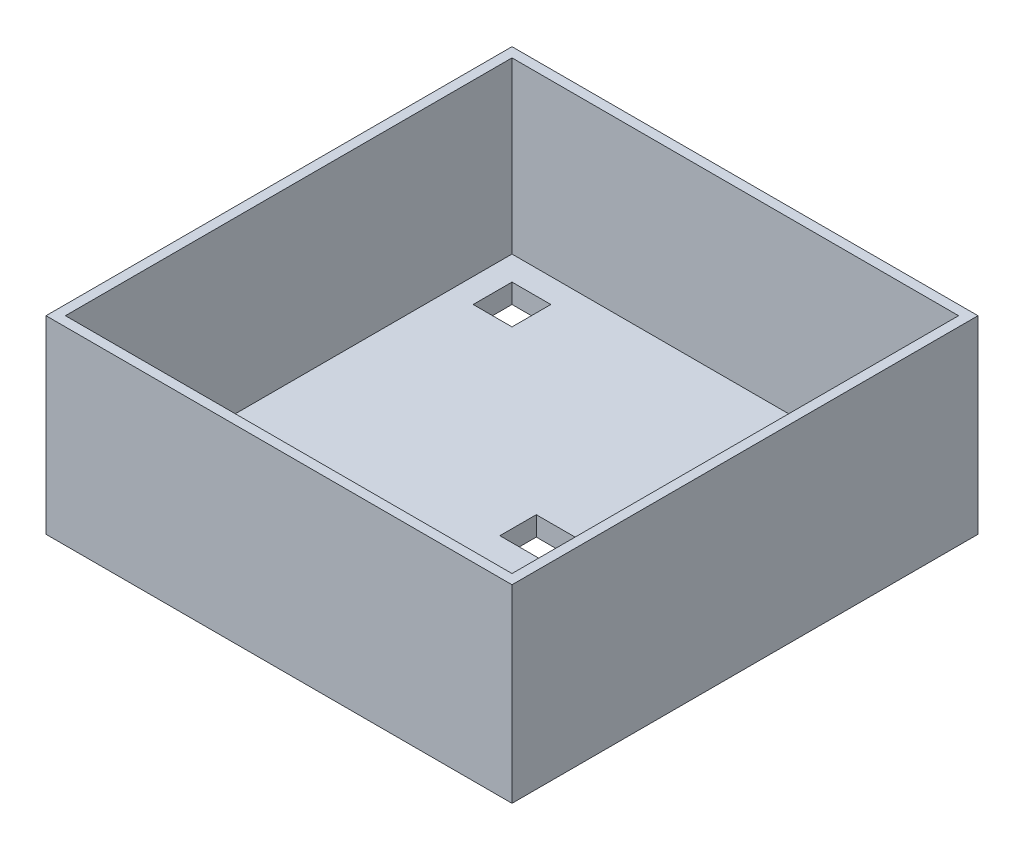
SolidWorks part; units mm, degrees
ref_plane "Front Plane" through (0, 0, 0) normal (0, 0, 1) x (1, 0, 0)
ref_plane "Top Plane" through (0, 0, 0) normal (0, 1, 0) x (1, 0, 0)
ref_plane "Right Plane" through (0, 0, 0) normal (1, 0, 0) x (0, 0, -1)
sketch "Sketch1" plane through (0, 0, 0) normal (0, 1, 0) x (1, 0, 0)
  line L1 (-50, -50) -> (50, -50)
  line L2 (-50, -50) -> (-50, 50)
  line L3 (-50, 50) -> (50, 50)
  line L4 (50, -50) -> (50, 50)
  line L5 (-50, -50) -> (50, 50) construction
  line L6 (-50, 50) -> (50, -50) construction
  point P0 (0, 0)
  dimension "D1" = 100
extrude "Boss-Extrude1" add sketch "Sketch1" along normal blind 4
sketch "Sketch2" plane through (0, 4, 0) normal (0, 1, 0) x (1, 0, 0)
  line L0 (46, -46) -> (46, 46)
  line L1 (46, 46) -> (-46, 46)
  line L2 (-46, 46) -> (-46, -46)
  line L3 (-46, -46) -> (46, -46)
  line L4 (50, -50) -> (50, 50)
  line L5 (50, 50) -> (-50, 50)
  line L6 (-50, 50) -> (-50, -50)
  line L7 (-50, -50) -> (50, -50)
  line L8 (50, -50) -> (50, 50)
  line L9 (50, 50) -> (-50, 50)
  line L10 (-50, 50) -> (-50, -50)
  line L11 (-50, -50) -> (50, -50)
  dimension "D1" = 0
  dimension "D2" = 4
extrude "Boss-Extrude2" add sketch "Sketch2" along normal blind 35
sketch "Sketch3" plane through (0, 0, -50) normal (0, 0, -1) x (-1, 0, 0)
  line L0 (-50, 39) -> (50, 39) construction
  line L1 (2, 35) -> (-2, 35)
  line L2 (2, 35) -> (2, 39)
  line L3 (2, 39) -> (-2, 39)
  line L4 (-2, 35) -> (-2, 39)
  line L5 (2, 35) -> (-2, 39) construction
  line L6 (2, 39) -> (-2, 35) construction
  point P0 (0, 37)
  dimension "D1" = 4
extrude "Cut-Extrude1" cut sketch "Sketch3" against normal up to surface (4 mm away) up to face at (0, 21.5, -46)
sketch "Sketch4" plane through (0, 4, 0) normal (0, 1, 0) x (1, 0, 0)
  line L1 (9.75, -0.5) -> (-1.75, -0.5)
  line L2 (9.75, -0.5) -> (9.75, -17)
  line L3 (9.75, -17) -> (-1.75, -17)
  line L4 (-1.75, -0.5) -> (-1.75, -17)
  line L5 (9.75, -0.5) -> (-1.75, -17) construction
  line L6 (9.75, -17) -> (-1.75, -0.5) construction
  line L7 (14, 19) -> (-6, 19)
  line L8 (14, 19) -> (14, -21)
  line L9 (14, -21) -> (-6, -21)
  line L10 (-6, 19) -> (-6, -21)
  line L11 (14, 19) -> (-6, -21) construction
  line L12 (14, -21) -> (-6, 19) construction
  line L17 (-46, -46) -> (46, -46) construction
  line L26 (46, -46) -> (46, 46) construction
  line L28 (12.25, -19.5) -> (7.25, -19.5)
  line L29 (12.25, -19.5) -> (12.25, -14.5)
  line L30 (12.25, -14.5) -> (7.25, -14.5)
  line L31 (7.25, -19.5) -> (7.25, -14.5)
  line L32 (12.25, -19.5) -> (7.25, -14.5) construction
  line L33 (12.25, -14.5) -> (7.25, -19.5) construction
  line L34 (-4.25, -19.5) -> (0.75, -19.5)
  line L35 (-4.25, -19.5) -> (-4.25, -14.5)
  line L36 (-4.25, -14.5) -> (0.75, -14.5)
  line L37 (0.75, -19.5) -> (0.75, -14.5)
  line L38 (-4.25, -19.5) -> (0.75, -14.5) construction
  line L39 (-4.25, -14.5) -> (0.75, -19.5) construction
  line L40 (12.25, 2) -> (7.25, 2)
  line L41 (12.25, 2) -> (12.25, -3)
  line L42 (12.25, -3) -> (7.25, -3)
  line L43 (7.25, 2) -> (7.25, -3)
  line L44 (12.25, 2) -> (7.25, -3) construction
  line L45 (12.25, -3) -> (7.25, 2) construction
  line L46 (-4.25, 2) -> (0.75, 2)
  line L47 (-4.25, 2) -> (-4.25, -3)
  line L48 (-4.25, -3) -> (0.75, -3)
  line L49 (0.75, 2) -> (0.75, -3)
  line L50 (-4.25, 2) -> (0.75, -3) construction
  line L51 (-4.25, -3) -> (0.75, 2) construction
  point P0 (4, -8.75)
  point P5 (4, -1)
  dimension "D1" = 11.5
  dimension "D2" = 16.5
  dimension "D3" = 32
  dimension "D4" = 25
  dimension "D5" = 40
  dimension "D6" = 20
  dimension "D7" = 4
  dimension "D8" = 2.5
  dimension "D9" = 2.5
extrude "Boss-Extrude3" add sketch "Sketch4" along normal blind 2.5 contours L49 L46 L47 L48 L4 L1 | L40 L43 L1 L2 L42 L41 | L31 L28 L29 L30 L2 L3 | L34 L37 L3 L4 L36 L35 region at (10.1667, 4, 0.0833) region at (-2.1667, 4, 0.0833) region at (10.1667, 4, 17.4167) region at (-2.1667, 4, 17.4167)
sketch "Sketch5" plane through (0, 4, 0) normal (0, 1, 0) x (1, 0, 0)
  line L1 (4, -13) -> (-1.75, -13)
  line L2 (4, -13) -> (4, -17)
  line L3 (4, -17) -> (-1.75, -17)
  line L4 (-1.75, -13) -> (-1.75, -17)
  line L5 (4, -13) -> (-1.75, -17) construction
  line L6 (4, -17) -> (-1.75, -13) construction
  point P0 (1.125, -15)
  dimension "D1" = 4
  dimension "D2" = 5.75
extrude "Cut-Extrude2" cut sketch "Sketch5" against normal up to surface (4 mm away) up to face at (0, 0, 0)
sketch "Sketch7" plane through (0, 4, 0) normal (0, 1, 0) x (1, 0, 0)
  line L0 (4, -13) -> (-1.75, -13) construction
  line L1 (-4.25, -19.5) -> (5, -19.5)
  line L2 (-4.25, -19.5) -> (-4.25, -12)
  line L3 (-4.25, -12) -> (5, -12)
  line L4 (5, -19.5) -> (5, -12)
  line L5 (4, -17) -> (4, -13) construction
  line L6 (-46, 46) -> (-46, -46) construction
  line L7 (12.25, 2) -> (3, 2)
  line L8 (12.25, 2) -> (12.25, -5.5)
  line L9 (12.25, -5.5) -> (3, -5.5)
  line L10 (3, 2) -> (3, -5.5)
  line L11 (-41, 33) -> (-33, 33)
  line L12 (-41, 33) -> (-41, 41)
  line L13 (-41, 41) -> (-33, 41)
  line L14 (-33, 33) -> (-33, 41)
  line L15 (-41, 33) -> (-33, 41) construction
  line L16 (-41, 41) -> (-33, 33) construction
  line L17 (2, 46) -> (-2, 46) construction
  point P9 (4, -15)
  point P15 (-37, 37)
  point P20 (0, 0)
  point P23 (-9.1198, 35)
  dimension "D1" = 1
  dimension "D2" = 1
  dimension "D3" = 9.25
  dimension "D4" = 7.5
  dimension "D5" = 5
  dimension "D6" = 8
  dimension "D7" = 5
extrude "Cut-Extrude3" cut sketch "Sketch7" against normal through all both and the other way through all
sketch "Sketch8" plane through (0, 4, 0) normal (0, 1, 0) x (1, 0, 0)
  line L1 (-4.7402, 2.9437) -> (1.459, 2.9437)
  line L2 (-4.7402, 2.9437) -> (-4.7402, -3.76)
  line L3 (-4.7402, -3.76) -> (1.459, -3.76)
  line L4 (1.459, 2.9437) -> (1.459, -3.76)
  line L5 (6.2886, -13.3471) -> (13.8574, -13.3471)
  line L6 (6.2886, -13.3471) -> (6.2886, -20.5555)
  line L7 (6.2886, -20.5555) -> (13.8574, -20.5555)
  line L8 (13.8574, -13.3471) -> (13.8574, -20.5555)
extrude "Cut-Extrude5" cut sketch "Sketch8" along normal blind 10
sketch "Sketch9" plane through (0, 0, -50) normal (0, 0, -1) x (-1, 0, 0)
  line L0 (-2, 39) -> (-2, 35) construction
  line L1 (-6, 23.5) -> (6, 23.5)
  line L2 (-6, 23.5) -> (-6, 15.5)
  line L3 (-6, 15.5) -> (6, 15.5)
  line L4 (6, 23.5) -> (6, 15.5)
  line L5 (2, 35) -> (2, 39) construction
  line L9 (-50, 39) -> (-2, 39) construction
  dimension "D1" = 4
  dimension "D2" = 4
  dimension "D3" = 8
  dimension "D4" = 15.5
extrude "Cut-Extrude6" [suppressed] cut sketch "Sketch9" against normal blind 10
sketch "Sketch10" plane through (0, 0, -50) normal (0, 0, -1) x (-1, 0, 0)
  line L1 (-2, 35) -> (2, 35)
  line L2 (-2, 35) -> (-2, 39)
  line L3 (-2, 39) -> (2, 39)
  line L4 (2, 35) -> (2, 39)
extrude "Boss-Extrude4" add sketch "Sketch10" against normal blind 4
sketch "Sketch11" plane through (0, 39, 0) normal (0, 1, 0) x (1, 0, 0)
  line L0 (-50, 50) -> (-50, -50) construction
  line L1 (-48, 48) -> (48, 48)
  line L2 (-48, 48) -> (-48, -48)
  line L3 (-48, -48) -> (48, -48)
  line L4 (48, 48) -> (48, -48)
  line L5 (50, 50) -> (-50, 50) construction
  line L6 (-46, -46) -> (46, -46) construction
  line L7 (46, -46) -> (46, 46) construction
  dimension "D1" = 2
  dimension "D2" = 2
  dimension "D3" = 2
  dimension "D4" = 2
extrude "Cut-Extrude7" cut sketch "Sketch11" against normal through all flip side to cut
sketch "Sketch12" [suppressed] plane through (0, 0, -48) normal (0, 0, -1) x (-1, 0, 0)
  line L0 (6, 15.5) -> (-6, 15.5) construction
  line L1 (-6, 23.5) -> (-4, 23.5)
  line L2 (-6, 23.5) -> (-6, 15.5)
  line L3 (-6, 15.5) -> (-4, 15.5)
  line L4 (-4, 23.5) -> (-4, 15.5)
  line L6 (6, 23.5) -> (4, 23.5)
  line L7 (6, 23.5) -> (6, 15.5)
  line L8 (6, 15.5) -> (4, 15.5)
  line L9 (4, 23.5) -> (4, 15.5)
  dimension "D1" = 2
  dimension "D2" = 2
extrude "Boss-Extrude5" [suppressed] add sketch "Sketch12" against normal blind 2
